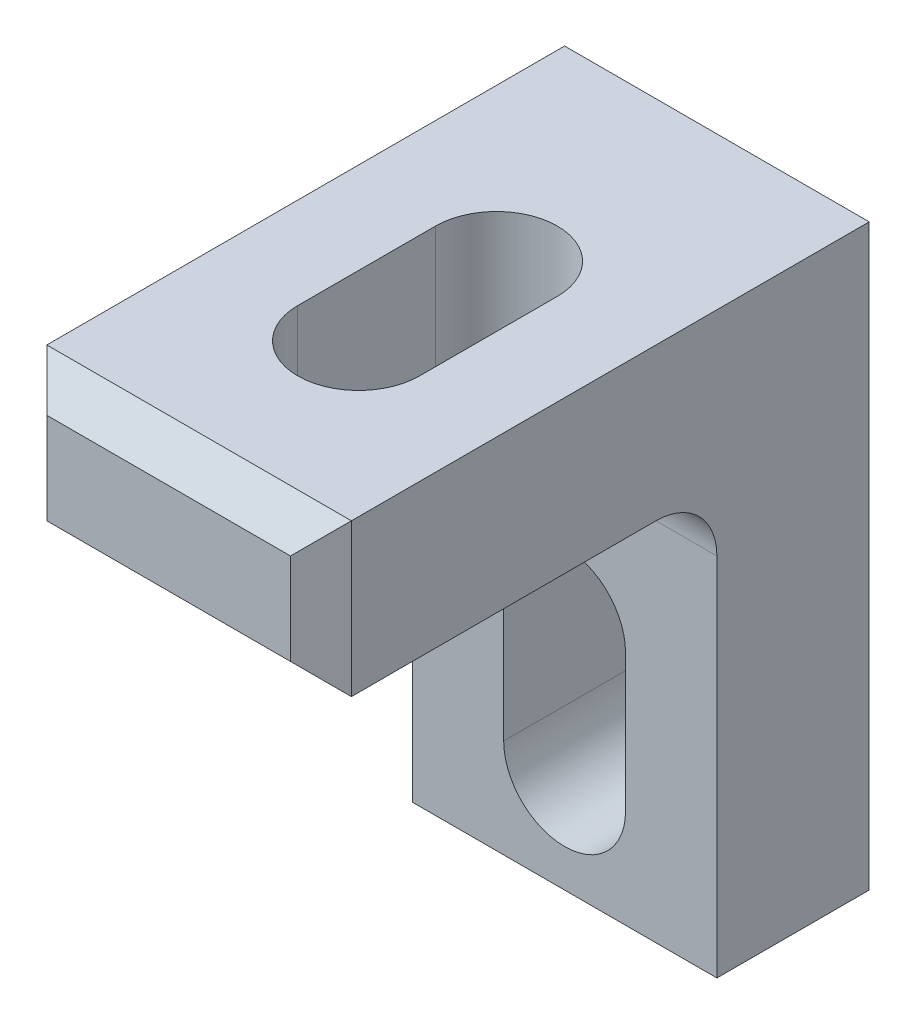
SolidWorks part; units mm, degrees
ref_plane "Front Plane" through (0, 0, 0) normal (0, 0, 1) x (1, 0, 0)
ref_plane "Top Plane" through (0, 0, 0) normal (0, 1, 0) x (1, 0, 0)
ref_plane "Right Plane" through (0, 0, 0) normal (1, 0, 0) x (0, 0, -1)
sketch "Sketch1" plane through (0, 0, 0) normal (0, 0, 1) x (1, 0, 0)
  line L0 (0, 0) -> (0, -61.6086) construction
  line L1 (0, -6.2381) -> (0, -10.7619) construction
  line L2 (-5, 0) -> (5, 0)
  line L3 (-5, 0) -> (-5, -15)
  line L4 (-5, -15) -> (5, -15)
  line L5 (5, 0) -> (5, -15)
  line L6 (2, -6.2381) -> (2, -10.7619)
  line L7 (-2, -6.2381) -> (-2, -10.7619)
  arc A0 (2, -6.2381) -> (-2, -6.2381) centre (0, -6.2381) ccw
  arc A1 (-2, -10.7619) -> (2, -10.7619) centre (0, -10.7619) ccw
  point P7 (0, 0)
  point P10 (0, -8.5)
  dimension "D1" = 10
  dimension "D5" = 6.2381
  dimension "D2" = 15
  dimension "D3" = 0
  dimension "D4" = 4
  dimension "D6" = 8.5
extrude "Boss-Extrude1" add sketch "Sketch1" along normal blind 5
ref_plane "Plane1" through (0, 0, 0) normal (0, 1, 0) x (1, 0, 0)
sketch "Sketch2" plane through (0, 0, 0) normal (0, 1, 0) x (1, 0, 0)
  line L0 (0, -11.7619) -> (0, -7.2381) construction
  line L1 (5, -18) -> (-5, -18)
  line L2 (5, -18) -> (5, -3)
  line L4 (-5, -18) -> (-5, -3)
  line L5 (-2, -11.7619) -> (-2, -7.2381)
  line L6 (2, -11.7619) -> (2, -7.2381)
  line L8 (-5, -3) -> (-5, 0)
  line L9 (-5, 0) -> (5, 0)
  line L10 (5, 0) -> (5, -3)
  arc A0 (-2, -11.7619) -> (2, -11.7619) centre (0, -11.7619) ccw
  arc A1 (2, -7.2381) -> (-2, -7.2381) centre (0, -7.2381) ccw
  point P4 (0, -18)
  point P7 (0, -9.5)
  dimension "D1" = 10
  dimension "D2" = 15
  dimension "D3" = 4
  dimension "D4" = 6.2381
  dimension "D5" = 8.5
extrude "Boss-Extrude2" add sketch "Sketch2" along normal blind 5
fillet "Fillet1" radius 2 1 edges
chamfer "Chamfer1" distance 1 angle 45 8 edges at (-5, -15, 2.5) (0, -15, 5) (5, -15, 2.5) (0, -15, 0) (-5, 2.5, 18) (0, 5, 18) (5, 2.5, 18) (0, 0, 18)
